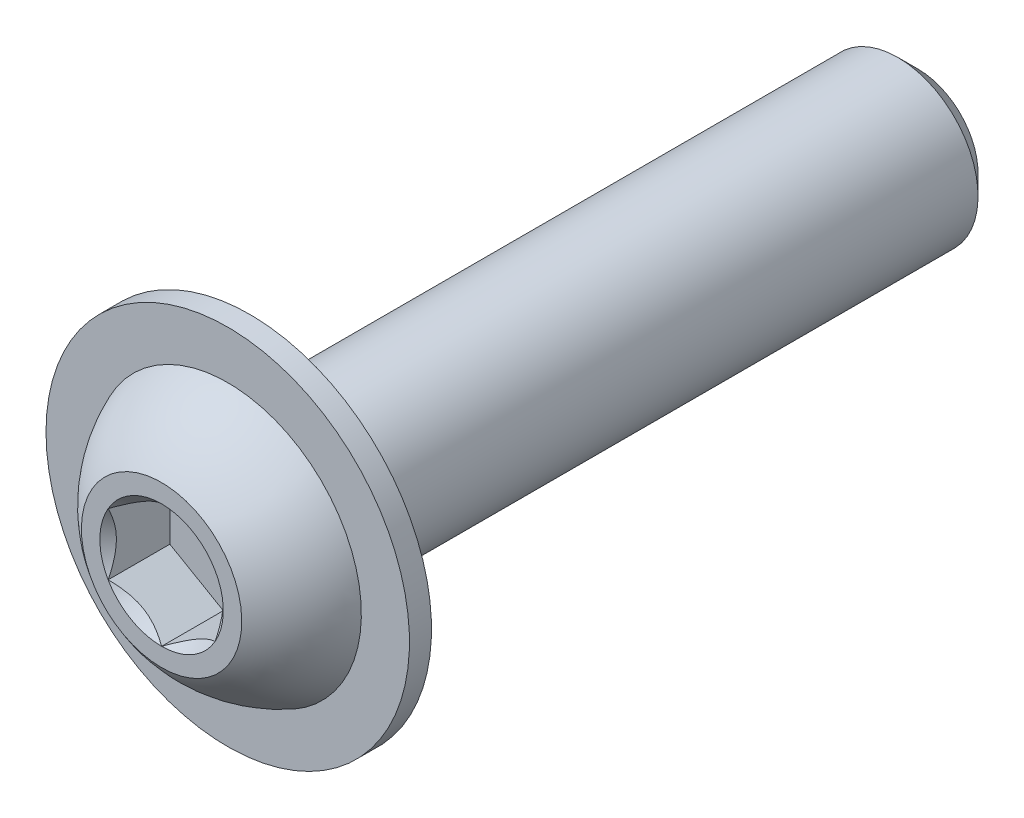
SolidWorks part; units mm, degrees
material "AISI 304"
ref_plane "Front" through (0, 0, 0) normal (0, 0, 1) x (1, 0, 0)
ref_plane "Top" through (0, 0, 0) normal (0, 1, 0) x (1, 0, 0)
ref_plane "Right" through (0, 0, 0) normal (1, 0, 0) x (0, 0, -1)
sketch "Sketch1" plane through (0, 0, 0) normal (1, 0, 0) x (0, 0, -1)
  line L2 (3.3, 3) -> (28.3, 3)
  line L3 (28.3, 3) -> (28.3, 0)
  line L4 (28.3, 0) -> (3.3, 0)
  line L6 (2.475, 5) -> (3.3, 5) construction
  line L7 (28.3, 3) -> (28.3, -3) construction
  line L8 (0, 0) -> (3.3, 0) construction
  line L9 (3.3, 5) -> (3.3, -5) construction
  line L11 (3.3, 3) -> (3.3, 0)
  line L13 (0, 2) -> (0, -2) construction
  line L14 (0, 2) -> (0, 3) construction
  line L15 (2.475, 5) -> (2.475, 6.8) construction
  line L16 (2.475, 6.8) -> (3.3, 6.8) construction
  line L17 (3.3, 6.8) -> (3.3, 5) construction
  line L18 (3.3, 6.8) -> (3.3, -6.8) construction
  arc A3 (0, 3) -> (2.475, 5) centre (4.4698, 0) cw construction
  dimension "D1" = 0.825
revolve "Revolve1" add sketch "Sketch1" angle 360 mid plane about L4
sketch "Sketch3" plane through (0, 0, -28.3) normal (0, 0, -1) x (-1, 0, 0)
  circle A0 centre (0, 0) radius 3
curve "Helix/Spiral1" pitch 1 height 26 turns 26
sketch "Sketch2" plane through (0, 0, 0) normal (1, 0, 0) x (0, 0, -1)
  line L0 (28.3, 3) -> (29.175, 3)
  line L1 (29.175, 3) -> (28.8, 2.3505)
  line L2 (28.8, 2.3505) -> (28.675, 2.3505)
  line L3 (28.675, 2.3505) -> (28.3, 3)
  line L4 (28.4875, 2.6752) -> (28.9875, 2.6752) construction
  dimension "D1" = 60
  dimension "D2" = 0.125
  dimension "D3" = 0.5
chamfer "Chamfer1" distance 0.75 angle 45 1 edges at (0, 3, -28.3)
sweep "Cut-Sweep1" [suppressed] cut profiles "Sketch2" path "Helix/Spiral1"
sketch "Sketch7" plane through (0, 0, 0) normal (1, 0, 0) x (0, 0, -1)
  line L6 (2.475, 5) -> (3.3, 5) construction
  line L8 (0, 0) -> (3.3, 0) construction
  line L11 (3.3, 5) -> (3.3, -5) construction
  line L12 (2.475, 5) -> (3.3, 5)
  line L13 (0, 0) -> (3.3, 0)
  line L14 (0, 2) -> (0, -2) construction
  line L15 (3.3, 5) -> (3.3, 0)
  line L16 (0, 3) -> (0, 0)
  arc A2 (2.475, 5) -> (0, 3) centre (4.4698, 0) ccw construction
  arc A3 (2.475, 5) -> (0, 3) centre (4.4698, 0) ccw
revolve "Revolve2" add sketch "Sketch7" angle 360 mid plane about L13
sketch "Sketch11" plane through (0, 0, -3.3) normal (0, 0, -1) x (-1, 0, 0)
  circle A0 centre (0, 0) radius 6.8
extrude "Boss-Extrude3" add sketch "Sketch11" against normal up to vertex (0.825 mm away) up to point (0, 5, -2.475)
sketch "Sketch5" plane through (0, 0, 0) normal (0, 0, 1) x (1, 0, 0)
  line L1 (2, -1.1547) -> (2, 1.1547)
  line L2 (2, 1.1547) -> (0, 2.3094)
  line L3 (0, 2.3094) -> (-2, 1.1547)
  line L4 (-2, 1.1547) -> (-2, -1.1547)
  line L5 (-2, -1.1547) -> (0, -2.3094)
  line L6 (0, -2.3094) -> (2, -1.1547)
  circle A0 centre (0, 0) radius 2 construction
extrude "Cut-Extrude2" cut sketch "Sketch5" against normal blind 2.31
sketch "Sketch6" plane through (0, 0, 0) normal (0, 0, 1) x (1, 0, 0)
  circle A0 centre (0, 0) radius 2.3094
extrude "Cut-Extrude3" cut sketch "Sketch6" against normal blind 2.31 draft 45
sketch "Sketch9" [suppressed] plane through (0, 0, -5.0546) normal (0, 0, 1) x (1, 0, 0)
  circle A2 centre (0, 0) radius 4.7625
extrude "Boss-Extrude2" [suppressed] add sketch "Sketch9" against normal offset from surface (6.35 mm away) 31.75 up to face at (0, 2.25, -28.3)
sketch "Sketch10" plane through (0, 0, 0) normal (1, 0, 0) x (0, 0, -1)
  line L0 (28.3, 3) -> (28.3, -3) construction
  point P0 (26.8, -3)
  dimension "D1" = 1.5
equation "\"D3@Helix/Spiral1\" = \"Lg@Sketch1\" + \"D4@Helix/Spiral1\""
equation "\"D2@Sketch2\" = \"D4@Helix/Spiral1\" * .125"
equation "\"D3@Sketch2\" = \"D4@Helix/Spiral1\" * .5"
equation "\"D1@Chamfer1\" = \"D4@Helix/Spiral1\" * .75"
equation "\"D1@Cut-Extrude2\" = \"Head Ht@Sketch1\" * .7"
equation "\"D1@Sketch1\" = \"Head Ht@Sketch1\" * .25"
equation "\"D1@Sketch10\" = \"D4@Helix/Spiral1\" * 1.5"
equation "\"D1@Cut-Extrude3\" = \"D1@Cut-Extrude2\""
